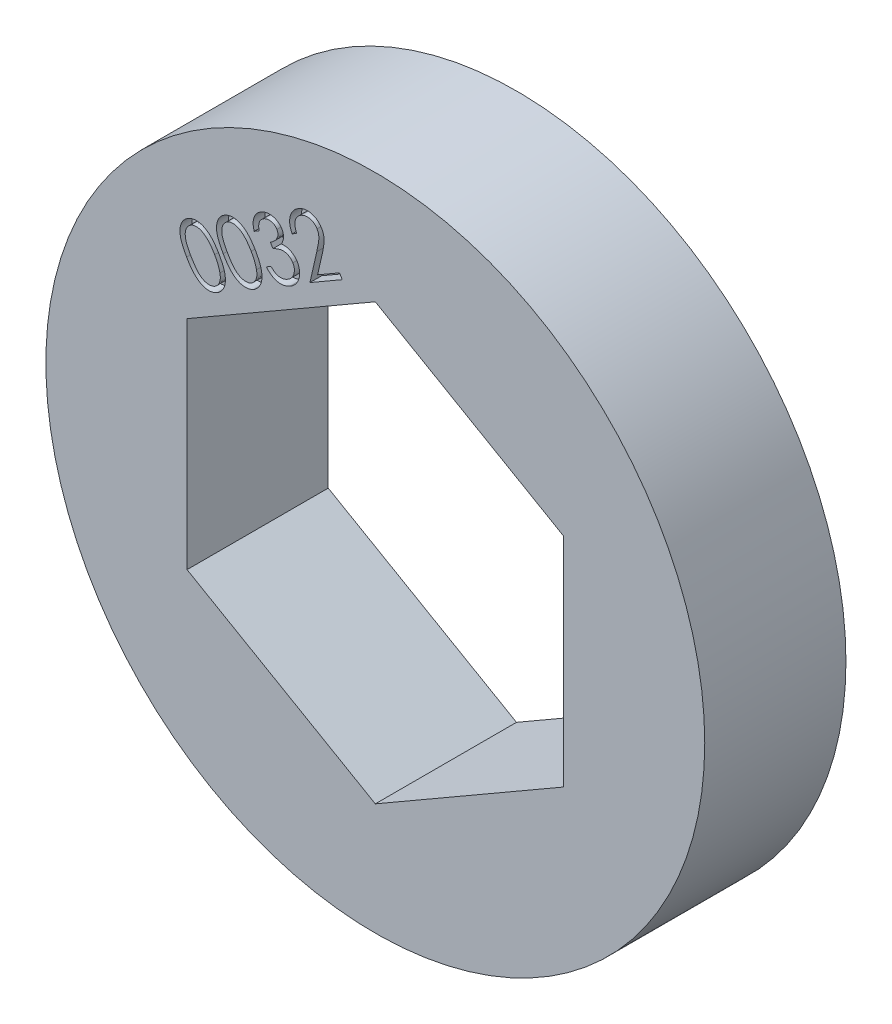
SolidWorks part; units mm, degrees
material "Nylon 101"
ref_plane "Front Plane" through (0, 0, 0) normal (0, 0, 1) x (1, 0, 0)
ref_plane "Top Plane" through (0, 0, 0) normal (0, 1, 0) x (1, 0, 0)
ref_plane "Right Plane" through (0, 0, 0) normal (1, 0, 0) x (0, 0, -1)
sketch "Sketch2" plane through (0, 0, 0) normal (0, 0, 1) x (1, 0, 0)
  line L1 (0, 7.3323) -> (-6.35, 3.6662)
  line L2 (-6.35, 3.6662) -> (-6.35, -3.6662)
  line L3 (-6.35, -3.6662) -> (0, -7.3323)
  line L4 (0, -7.3323) -> (6.35, -3.6662)
  line L5 (6.35, -3.6662) -> (6.35, 3.6662)
  line L6 (6.35, 3.6662) -> (0, 7.3323)
  circle A0 centre (0, 0) radius 6.35 construction
  circle A1 centre (0, 0) radius 11.1125
  dimension "D1" = 22.225
  dimension ".5" = 12.7
extrude "Boss-Extrude1" add sketch "Sketch2" along normal blind 4.7625
sketch "Sketch3" plane through (0, 0, 4.7625) normal (0, 0, 1) x (1, 0, 0)
  line L0 (-6.727, 4.1817) -> (-0.2842, 7.9015) construction
  line L1 (0, 7.3323) -> (-6.35, 3.6662) construction
  text T0 "0032\r\n" font "Century Gothic" height in points 7
  point P4 (-0.2842, 7.9015)
  point P5 (-6.727, 4.1817)
  dimension "D1" = 0.635
extrude "Cut-Extrude1" cut sketch "Sketch3" against normal blind 0.4
